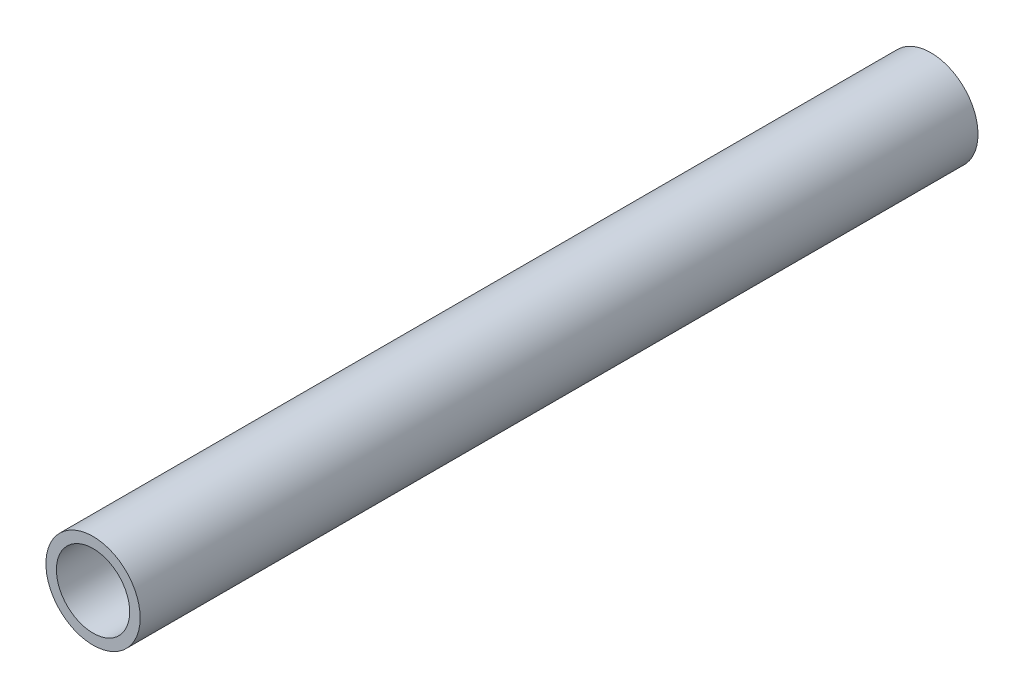
SolidWorks part; units mm, degrees
material "Copper"
ref_plane "Спереди" through (0, 0, 0) normal (0, 0, 1) x (1, 0, 0)
ref_plane "Сверху" through (0, 0, 0) normal (0, 1, 0) x (1, 0, 0)
ref_plane "Справа" through (0, 0, 0) normal (1, 0, 0) x (0, 0, -1)
sketch "Sketch1" plane through (0, 0, 0) normal (0, 0, 1) x (1, 0, 0)
  circle A0 centre (0, 0) radius 3.5
  circle A1 centre (0, 0) radius 4.5
  dimension "D1" = 1
  dimension "D2" = 7
extrude "Boss-Extrude1" add sketch "Sketch1" along normal blind 80
